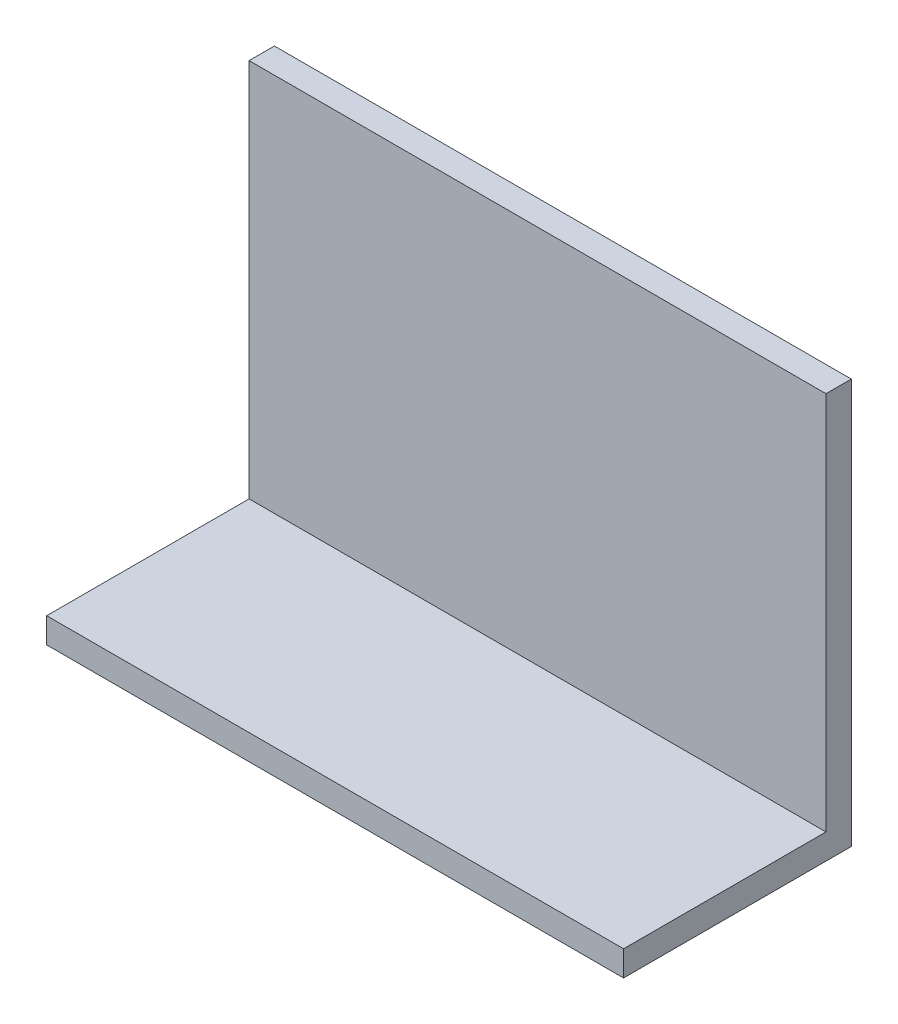
SolidWorks part; units mm, degrees
ref_plane "正面" through (0, 0, 0) normal (0, 0, 1) x (1, 0, 0)
ref_plane "平面" through (0, 0, 0) normal (0, 1, 0) x (1, 0, 0)
ref_plane "右側面" through (0, 0, 0) normal (1, 0, 0) x (0, 0, -1)
sketch "ｽｹｯﾁ1" plane through (0, 0, 0) normal (0, 1, 0) x (1, 0, 0)
  line L1 (-57, 20) -> (57, 20)
  line L2 (-57, 20) -> (-57, -20)
  line L3 (-57, -20) -> (57, -20)
  line L4 (57, 20) -> (57, -20)
  line L5 (-57, 20) -> (57, -20) construction
  line L6 (-57, -20) -> (57, 20) construction
  point P0 (0, 0)
  dimension "D1" = 114
  dimension "D2" = 40
extrude "ﾎﾞｽ - 押し出し1" add sketch "ｽｹｯﾁ1" along normal blind 5
sketch "ｽｹｯﾁ2" plane through (0, 0, -20) normal (0, 0, -1) x (-1, 0, 0)
  line L0 (57, 5) -> (57, 0) construction
  line L1 (-57, 0) -> (57, 0)
  line L2 (-57, 0) -> (-57, 80)
  line L3 (-57, 80) -> (57, 80)
  line L4 (57, 0) -> (57, 80)
  dimension "D1" = 80
extrude "ﾎﾞｽ - 押し出し2" add sketch "ｽｹｯﾁ2" along normal blind 5
